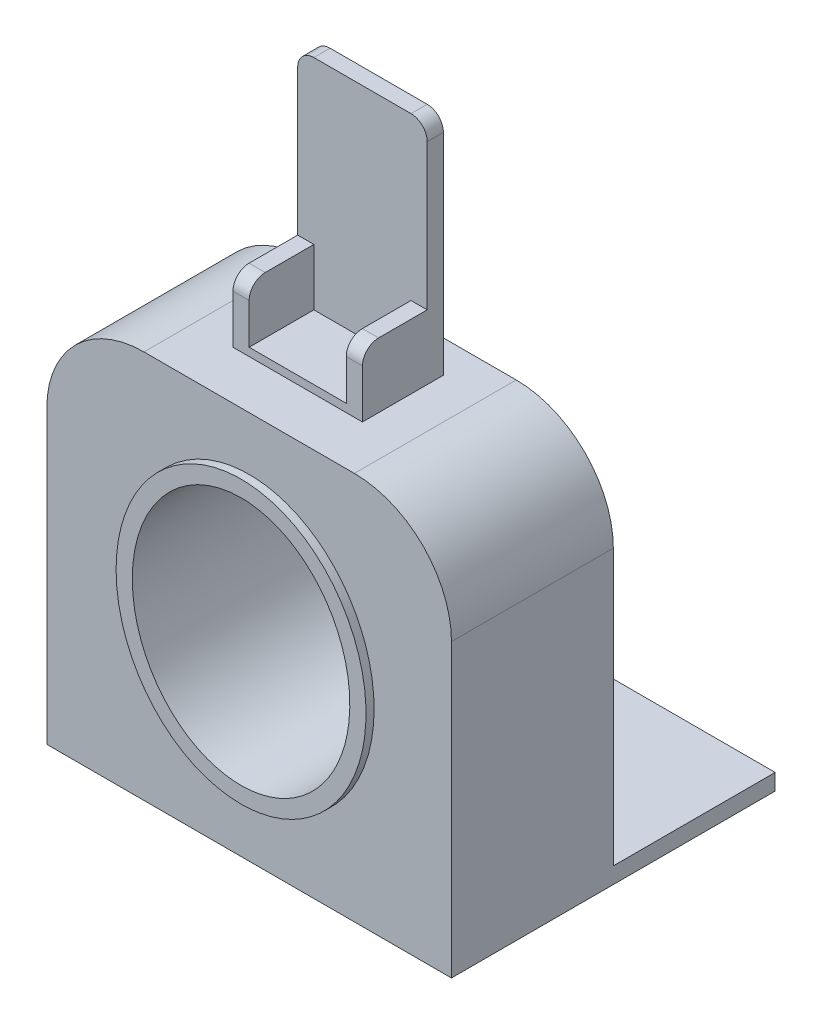
SolidWorks part; units mm, degrees
ref_plane "Front" through (0, 0, 0) normal (0, 0, 1) x (1, 0, 0)
ref_plane "Top" through (0, 0, 0) normal (0, 1, 0) x (1, 0, 0)
ref_plane "Right" through (0, 0, 0) normal (1, 0, 0) x (0, 0, -1)
sketch "Croquis1" plane through (0, 0, 0) normal (0, 1, 0) x (1, 0, 0)
  line L0 (0, 100) -> (250, 100)
  line L1 (0, 0) -> (250, 0)
  line L2 (0, 0) -> (0, 200)
  line L3 (0, 200) -> (250, 200)
  line L4 (250, 0) -> (250, 200)
  dimension "D1" = 200
  dimension "D2" = 250
extrude "Saliente-Extruir1" add sketch "Croquis1" along normal blind 240 contours L1 L4 L0 L2 region at (125, 0, -50)
extrude "Saliente-Extruir2" add sketch "Croquis1<3>" along normal blind 10 contours L0 L4 L3 L2 region at (125, 0, -150)
sketch "Croquis1<3>" plane through (0, 0, 0) normal (0, 1, 0) x (1, 0, 0) same geometry as "Croquis1"
sketch "Croquis7" plane through (0, 0, 0) normal (0, 0, 1) x (1, 0, 0)
  line L0 (0, 240) -> (250, 0) construction
  ellipse E0 centre (125, 120) end of major axis (125, 196.9723) minor radius 67.2042
fillet "Redondeo2" radius 60 2 edges at (0, 240, -50) (250, 240, -50)
extrude "Cortar-Extruir4" cut sketch "Croquis7" against normal blind 143
sketch "Croquis8" plane through (0, 0, 0) normal (0, 0, 1) x (1, 0, 0)
  ellipse E1 centre (125, 120) end of major axis (125, 196.9723) minor radius 67.2042
  ellipse E2 centre (125, 120) end of major axis (125, 196.9723) minor radius 67.2042 construction
  spline S0 degree 3 poles (124.3208, 33.0277) (127.7169, 33.0277) (130.4046, 33.1884) (135.7242, 33.8166) (138.3561, 34.284) (143.5649, 35.5215) (146.1418, 36.2915) (149.3279, 37.4467) (149.9634, 37.6874) (151.2227, 38.185) (151.8475, 38.4422) (153.7079, 39.2388) (154.9293, 39.8029) (158.5386, 41.5919) (160.8716, 42.9131) (165.3959, 45.8048) (167.5882, 47.3761) (171.8265, 50.7642) (173.8405, 52.5551) (177.6713, 56.3178) (179.4882, 58.2898) (182.9318, 62.4085) (184.5585, 64.5553) (186.8569, 67.9058) (187.5967, 69.0407) (189.0173, 71.3334) (189.6993, 72.4931) (192.9719, 78.3562) (195.154, 83.252) (197.3588, 89.6178) (197.7734, 90.9034) (198.5495, 93.4995) (198.9085, 94.8013) (199.9002, 98.7183) (200.4482, 101.3446) (201.7633, 109.2674) (202.2045, 114.6071) (202.2042, 121.3551) (202.1761, 122.7113) (202.0643, 125.4105) (201.9807, 126.7546) (201.6481, 130.7711) (201.3174, 133.4275) (200.0009, 141.3331) (198.6942, 146.5196) (196.4905, 152.891) (196.0197, 154.1629) (195.0256, 156.6782) (194.5029, 157.9202) (192.8586, 161.6001) (191.6609, 163.9917) (187.7617, 170.9801) (184.7573, 175.3927) (180.876, 180.0521) (180.4377, 180.5655) (179.5468, 181.5837) (179.0934, 182.0891) (177.7175, 183.5854) (176.7798, 184.5556) (173.9054, 187.3853) (171.9078, 189.1639) (167.748, 192.5027) (165.5859, 194.0631) (161.0906, 196.9567) (158.7573, 198.2901) (155.7258, 199.8043) (155.1128, 200.0998) (153.8834, 200.6715) (153.2661, 200.9481) (151.4069, 201.7501) (150.1574, 202.2478) (146.379, 203.631) (143.8205, 204.4067) (138.6233, 205.6626) (135.9847, 206.1427) (132.6342, 206.5503) (131.9614, 206.6221) (130.6107, 206.7462) (129.9317, 206.7984) (127.9005, 206.9244) (126.5502, 206.968) (122.5108, 206.98) (119.833, 206.83) (114.5073, 206.2196) (111.8594, 205.7593) (107.9102, 204.8325) (106.5935, 204.4828) (103.9947, 203.7114) (102.7117, 203.2898) (98.9107, 201.9204) (96.4405, 200.8683) (91.623, 198.4955) (89.2758, 197.1747) (85.8471, 194.9926) (84.7187, 194.2309) (82.5174, 192.6581) (81.4412, 191.8452) (78.2835, 189.3291) (76.2729, 187.5489) (72.4329, 183.7915) (70.6036, 181.8141) (67.9941, 178.7017) (67.1458, 177.6385) (65.5099, 175.4841) (64.7201, 174.3907) (62.4326, 171.0631) (61.0166, 168.7818) (58.3941, 164.0985) (57.1876, 161.6964) (55.5329, 158.0037) (55.0073, 156.7579) (54.008, 154.2362) (53.537, 152.9668) (51.3265, 146.5932) (50.0113, 141.394) (48.6857, 133.4519) (48.3524, 130.7805) (48.0179, 126.7368) (47.9341, 125.3811) (47.8231, 122.6806) (47.7956, 121.3332) (47.7964, 114.6103) (48.2352, 109.2766) (49.552, 101.3431) (50.1014, 98.7098) (51.0979, 94.7774) (51.4596, 93.4674) (52.2346, 90.8781) (52.6484, 89.5961) (54.8483, 83.2485) (57.0233, 78.3691) (60.9323, 71.3594) (62.3438, 69.0748) (64.634, 65.7306) (65.4287, 64.6265) (67.0631, 62.4671) (67.9027, 61.4114) (70.4883, 58.3159) (72.3011, 56.3475) (76.1072, 52.6039) (78.1004, 50.8287) (82.2751, 47.4796) (84.4565, 45.9057) (87.3099, 44.074) (87.8879, 43.7138) (89.0499, 43.0117) (89.6343, 42.6694) (91.3975, 41.6685) (92.5864, 41.0362) (96.1931, 39.243) (98.651, 38.1859) (103.6748, 36.3519) (106.2407, 35.5751) (110.1744, 34.6298) (111.4998, 34.3514) (114.1799, 33.8708) (115.5244, 33.6704) (118.2196, 33.3497) (119.5707, 33.2292) (121.6027, 33.1084) (122.2809, 33.0782) (123.6391, 33.0378) (124.3208, 33.0277) (127.7169, 33.0277) (130.4046, 33.1884) knots -0.003906 -0.003906 0 0 0.015625 0.015625 0.03125 0.03125 0.046875 0.046875 0.050781 0.050781 0.054688 0.054688 0.0625 0.0625 0.078125 0.078125 0.09375 0.09375 0.109375 0.109375 0.125 0.125 0.140625 0.140625 0.148438 0.148438 0.15625 0.15625 0.1875 0.1875 0.195313 0.195313 0.203125 0.203125 0.21875 0.21875 0.25 0.25 0.257813 0.257813 0.265625 0.265625 0.28125 0.28125 0.3125 0.3125 0.320313 0.320313 0.328125 0.328125 0.34375 0.34375 0.375 0.375 0.378906 0.378906 0.382813 0.382813 0.390625 0.390625 0.40625 0.40625 0.421875 0.421875 0.4375 0.4375 0.441406 0.441406 0.445313 0.445313 0.453125 0.453125 0.46875 0.46875 0.484375 0.484375 0.488281 0.488281 0.492188 0.492188 0.5 0.5 0.515625 0.515625 0.53125 0.53125 0.539063 0.539063 0.546875 0.546875 0.5625 0.5625 0.578125 0.578125 0.585938 0.585938 0.59375 0.59375 0.609375 0.609375 0.625 0.625 0.632813 0.632813 0.640625 0.640625 0.65625 0.65625 0.671875 0.671875 0.679688 0.679688 0.6875 0.6875 0.71875 0.71875 0.734375 0.734375 0.742188 0.742188 0.75 0.75 0.78125 0.78125 0.796875 0.796875 0.804688 0.804688 0.8125 0.8125 0.84375 0.84375 0.859375 0.859375 0.867188 0.867188 0.875 0.875 0.890625 0.890625 0.90625 0.90625 0.921875 0.921875 0.925781 0.925781 0.929688 0.929688 0.9375 0.9375 0.953125 0.953125 0.96875 0.96875 0.976563 0.976563 0.984375 0.984375 0.992188 0.992188 0.996094 0.996094 1 1 1.015625 1.015625 1.03125 only from (125, 33.0277) to (125, 33.0277)
  spline S1 degree 3 poles (124.3208, 33.0277) (127.7169, 33.0277) (130.4046, 33.1884) (135.7242, 33.8166) (138.3561, 34.284) (143.5649, 35.5215) (146.1418, 36.2915) (149.3279, 37.4467) (149.9634, 37.6874) (151.2227, 38.185) (151.8475, 38.4422) (153.7079, 39.2388) (154.9293, 39.8029) (158.5386, 41.5919) (160.8716, 42.9131) (165.3959, 45.8048) (167.5882, 47.3761) (171.8265, 50.7642) (173.8405, 52.5551) (177.6713, 56.3178) (179.4882, 58.2898) (182.9318, 62.4085) (184.5585, 64.5553) (186.8569, 67.9058) (187.5967, 69.0407) (189.0173, 71.3334) (189.6993, 72.4931) (192.9719, 78.3562) (195.154, 83.252) (197.3588, 89.6178) (197.7734, 90.9034) (198.5495, 93.4995) (198.9085, 94.8013) (199.9002, 98.7183) (200.4482, 101.3446) (201.7633, 109.2674) (202.2045, 114.6071) (202.2042, 121.3551) (202.1761, 122.7113) (202.0643, 125.4105) (201.9807, 126.7546) (201.6481, 130.7711) (201.3174, 133.4275) (200.0009, 141.3331) (198.6942, 146.5196) (196.4905, 152.891) (196.0197, 154.1629) (195.0256, 156.6782) (194.5029, 157.9202) (192.8586, 161.6001) (191.6609, 163.9917) (187.7617, 170.9801) (184.7573, 175.3927) (180.876, 180.0521) (180.4377, 180.5655) (179.5468, 181.5837) (179.0934, 182.0891) (177.7175, 183.5854) (176.7798, 184.5556) (173.9054, 187.3853) (171.9078, 189.1639) (167.748, 192.5027) (165.5859, 194.0631) (161.0906, 196.9567) (158.7573, 198.2901) (155.7258, 199.8043) (155.1128, 200.0998) (153.8834, 200.6715) (153.2661, 200.9481) (151.4069, 201.7501) (150.1574, 202.2478) (146.379, 203.631) (143.8205, 204.4067) (138.6233, 205.6626) (135.9847, 206.1427) (132.6342, 206.5503) (131.9614, 206.6221) (130.6107, 206.7462) (129.9317, 206.7984) (127.9005, 206.9244) (126.5502, 206.968) (122.5108, 206.98) (119.833, 206.83) (114.5073, 206.2196) (111.8594, 205.7593) (107.9102, 204.8325) (106.5935, 204.4828) (103.9947, 203.7114) (102.7117, 203.2898) (98.9107, 201.9204) (96.4405, 200.8683) (91.623, 198.4955) (89.2758, 197.1747) (85.8471, 194.9926) (84.7187, 194.2309) (82.5174, 192.6581) (81.4412, 191.8452) (78.2835, 189.3291) (76.2729, 187.5489) (72.4329, 183.7915) (70.6036, 181.8141) (67.9941, 178.7017) (67.1458, 177.6385) (65.5099, 175.4841) (64.7201, 174.3907) (62.4326, 171.0631) (61.0166, 168.7818) (58.3941, 164.0985) (57.1876, 161.6964) (55.5329, 158.0037) (55.0073, 156.7579) (54.008, 154.2362) (53.537, 152.9668) (51.3265, 146.5932) (50.0113, 141.394) (48.6857, 133.4519) (48.3524, 130.7805) (48.0179, 126.7368) (47.9341, 125.3811) (47.8231, 122.6806) (47.7956, 121.3332) (47.7964, 114.6103) (48.2352, 109.2766) (49.552, 101.3431) (50.1014, 98.7098) (51.0979, 94.7774) (51.4596, 93.4674) (52.2346, 90.8781) (52.6484, 89.5961) (54.8483, 83.2485) (57.0233, 78.3691) (60.9323, 71.3594) (62.3438, 69.0748) (64.634, 65.7306) (65.4287, 64.6265) (67.0631, 62.4671) (67.9027, 61.4114) (70.4883, 58.3159) (72.3011, 56.3475) (76.1072, 52.6039) (78.1004, 50.8287) (82.2751, 47.4796) (84.4565, 45.9057) (87.3099, 44.074) (87.8879, 43.7138) (89.0499, 43.0117) (89.6343, 42.6694) (91.3975, 41.6685) (92.5864, 41.0362) (96.1931, 39.243) (98.651, 38.1859) (103.6748, 36.3519) (106.2407, 35.5751) (110.1744, 34.6298) (111.4998, 34.3514) (114.1799, 33.8708) (115.5244, 33.6704) (118.2196, 33.3497) (119.5707, 33.2292) (121.6027, 33.1084) (122.2809, 33.0782) (123.6391, 33.0378) (124.3208, 33.0277) (127.7169, 33.0277) (130.4046, 33.1884) knots -0.003906 -0.003906 0 0 0.015625 0.015625 0.03125 0.03125 0.046875 0.046875 0.050781 0.050781 0.054688 0.054688 0.0625 0.0625 0.078125 0.078125 0.09375 0.09375 0.109375 0.109375 0.125 0.125 0.140625 0.140625 0.148438 0.148438 0.15625 0.15625 0.1875 0.1875 0.195313 0.195313 0.203125 0.203125 0.21875 0.21875 0.25 0.25 0.257813 0.257813 0.265625 0.265625 0.28125 0.28125 0.3125 0.3125 0.320313 0.320313 0.328125 0.328125 0.34375 0.34375 0.375 0.375 0.378906 0.378906 0.382813 0.382813 0.390625 0.390625 0.40625 0.40625 0.421875 0.421875 0.4375 0.4375 0.441406 0.441406 0.445313 0.445313 0.453125 0.453125 0.46875 0.46875 0.484375 0.484375 0.488281 0.488281 0.492188 0.492188 0.5 0.5 0.515625 0.515625 0.53125 0.53125 0.539063 0.539063 0.546875 0.546875 0.5625 0.5625 0.578125 0.578125 0.585938 0.585938 0.59375 0.59375 0.609375 0.609375 0.625 0.625 0.632813 0.632813 0.640625 0.640625 0.65625 0.65625 0.671875 0.671875 0.679688 0.679688 0.6875 0.6875 0.71875 0.71875 0.734375 0.734375 0.742188 0.742188 0.75 0.75 0.78125 0.78125 0.796875 0.796875 0.804688 0.804688 0.8125 0.8125 0.84375 0.84375 0.859375 0.859375 0.867188 0.867188 0.875 0.875 0.890625 0.890625 0.90625 0.90625 0.921875 0.921875 0.925781 0.925781 0.929688 0.929688 0.9375 0.9375 0.953125 0.953125 0.96875 0.96875 0.976563 0.976563 0.984375 0.984375 0.992188 0.992188 0.996094 0.996094 1 1 1.015625 1.015625 1.03125 only from (125, 33.0277) to (125, 33.0277)
  dimension "D1" = 10
extrude "Saliente-Extruir3" add sketch "Croquis8" along normal blind 5
sketch "Croquis10" plane through (0, 240, 0) normal (0, 1, 0) x (1, 0, 0)
  line L0 (125, 100) -> (125, 0) construction
  line L5 (60, 100) -> (190, 100) construction
  line L6 (60, 0) -> (190, 0) construction
  line L7 (60, 50) -> (190, 50) construction
  line L8 (60, 100) -> (60, 0) construction
  line L9 (190, 0) -> (190, 100) construction
  line L10 (85, 70) -> (85, 80)
  line L11 (85, 30) -> (165, 30)
  line L12 (85, 30) -> (85, 70)
  line L13 (85, 70) -> (165, 70)
  line L14 (165, 30) -> (165, 70)
  line L15 (85, 30) -> (165, 70) construction
  line L16 (85, 70) -> (165, 30) construction
  line L17 (85, 80) -> (165, 80)
  line L18 (165, 80) -> (165, 70)
  line L19 (85, 30) -> (95, 30)
  line L20 (95, 30) -> (95, 70)
  line L21 (165, 30) -> (155, 30)
  line L22 (155, 30) -> (155, 70)
  point P0 (125, 50)
  dimension "D1" = 40
  dimension "D2" = 80
  dimension "D3" = 10
  dimension "D4" = 10
  dimension "D5" = 10
extrude "Saliente-Extruir4" add sketch "Croquis10" along normal blind 140 contours L18 L17 L10 L13 region at (125, 240, -75)
extrude "Saliente-Extruir5" add sketch "Croquis10<4>" along normal blind 5 contours L11 L22 L13 L20 region at (125, 240, -50)
sketch "Croquis10<4>" plane through (0, 240, 0) normal (0, 1, 0) x (1, 0, 0) same geometry as "Croquis10"
extrude "Saliente-Extruir6" add sketch "Croquis10<7>" along normal blind 40 contours L22 L11 L14 L13 | L11 L20 L13 L12 region at (90, 240, -50) region at (160, 240, -50)
sketch "Croquis10<7>" plane through (0, 240, 0) normal (0, 1, 0) x (1, 0, 0) same geometry as "Croquis10"
fillet "Redondeo3" radius 10 4 edges at (90, 280, -30) (160, 280, -30) (85, 380, -75) (165, 380, -75)
